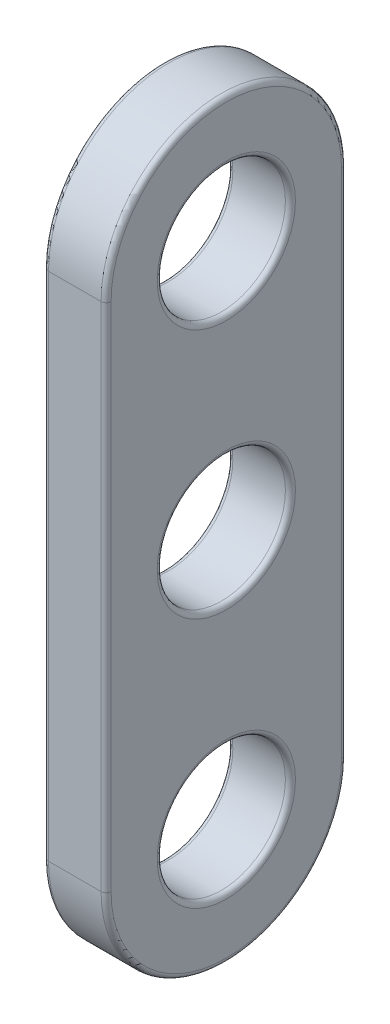
SolidWorks part; units mm, degrees
material "ABS"
ref_plane "Front Plane" through (0, 0, 0) normal (0, 0, 1) x (1, 0, 0)
ref_plane "Top Plane" through (0, 0, 0) normal (0, 1, 0) x (1, 0, 0)
ref_plane "Right Plane" through (0, 0, 0) normal (1, 0, 0) x (0, 0, -1)
sketch "Sketch1" plane through (0, 0, 0) normal (1, 0, 0) x (0, 0, -1)
  line L0 (0, 12.7) -> (0, -12.7) construction
  line L2 (-6.096, 19.05) -> (6.096, 19.05)
  line L3 (-6.096, 19.05) -> (-6.096, -19.05)
  line L4 (-6.096, -19.05) -> (6.096, -19.05)
  line L5 (6.096, 19.05) -> (6.096, -19.05)
  line L6 (-6.096, 19.05) -> (6.096, -19.05) construction
  line L7 (-6.096, -19.05) -> (6.096, 19.05) construction
  circle A0 centre (0, 12.7) radius 3.2512
  circle A1 centre (0, -12.7) radius 3.2512
  point P5 (0, 0)
  dimension "D2" = 6.5024
  dimension "D1" = 25.4
  dimension "D3" = 38.1
  dimension "D4" = 12.192
extrude "Boss-Extrude1" add sketch "Sketch1" along normal mid plane 3.175
fillet "Fillet1" 2 edges at (0, 19.05, 6.096) (0, 19.05, -6.096) type full round first side face at (0, 0, 6.096) second side face at (0, 0, -6.096) middle face at (0, 19.05, 0)
fillet "Fillet2" 2 edges at (0, -19.05, 6.096) (0, -19.05, -6.096) type full round first side face at (0, -3.048, 6.096) second side face at (0, -3.048, -6.096) middle face at (0, -19.05, 0)
sketch "Sketch2" plane through (1.5875, 0, 0) normal (1, 0, 0) x (0, 0, -1)
  circle A0 centre (0, 0) radius 3.2512
  dimension "D1" = 6.5024
extrude "Cut-Extrude1" cut sketch "Sketch2" against normal through all
fillet "Fillet3" radius 0.254 14 edges at (1.5875, 0, -3.2512) (-1.5875, 0, -3.2512) (-1.5875, -12.7, -3.2512) (1.5875, -12.7, -3.2512) (1.5875, 12.7, -3.2512) (-1.5875, 0, -6.096) (-1.5875, 0, 6.096) (1.5875, 0, -6.096) (1.5875, 0, 6.096) (-1.5875, -19.05, 0) (1.5875, -19.05, 0) (-1.5875, 12.7, -3.2512) (-1.5875, 19.05, 0) (1.5875, 19.05, 0)
